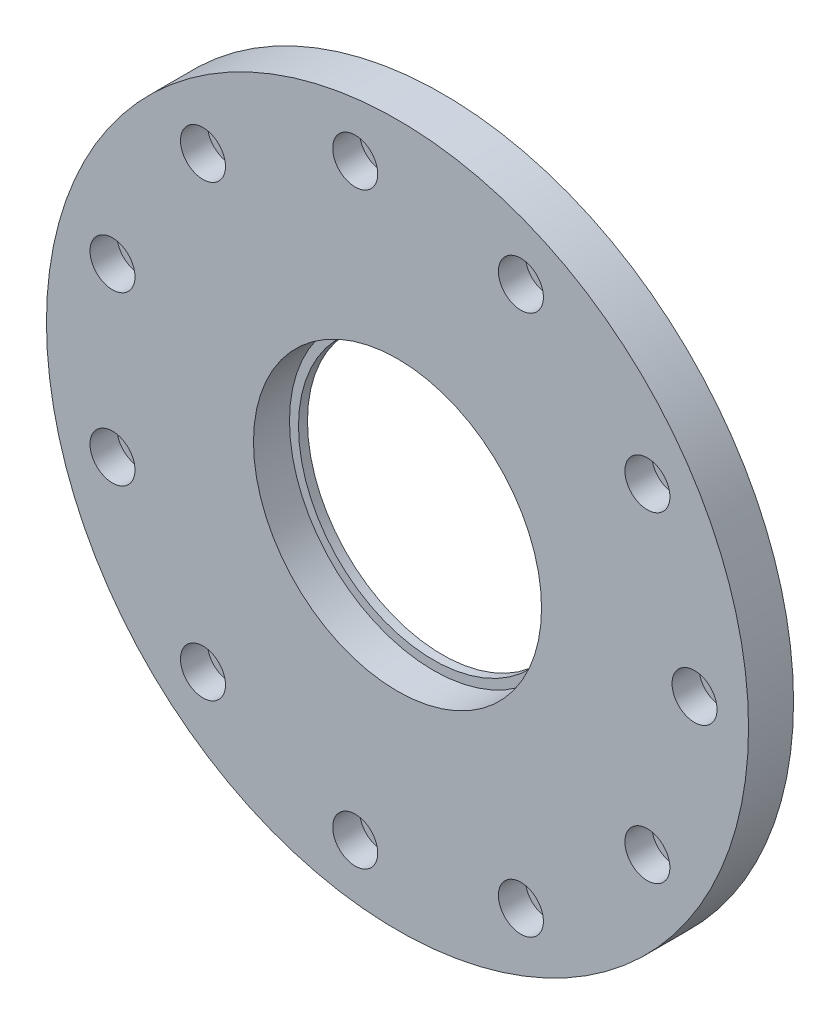
SolidWorks part; units mm, degrees
ref_plane "Front Plane" through (0, 0, 0) normal (0, 0, 1) x (1, 0, 0)
ref_plane "Top Plane" through (0, 0, 0) normal (0, 1, 0) x (1, 0, 0)
ref_plane "Right Plane" through (0, 0, 0) normal (1, 0, 0) x (0, 0, -1)
sketch "Sketch1" plane through (0, 0, 0) normal (0, 0, 1) x (1, 0, 0)
  circle A0 centre (0, 0) radius 39
  circle A1 centre (0, 0) radius 33 construction
  circle A2 centre (33, 0) radius 2.5
  circle A3 centre (27.7614, -17.8411) radius 2.5
  circle A4 centre (13.7087, -30.0179) radius 2.5
  circle A5 centre (-4.6964, -32.6641) radius 2.5
  circle A6 centre (-21.6104, -24.9397) radius 2.5
  circle A7 centre (-31.6633, -9.2972) radius 2.5
  circle A8 centre (-31.6633, 9.2972) radius 2.5
  circle A9 centre (-21.6104, 24.9397) radius 2.5
  circle A10 centre (-4.6964, 32.6641) radius 2.5
  circle A11 centre (13.7087, 30.0179) radius 2.5
  circle A12 centre (27.7614, 17.8411) radius 2.5
  circle A13 centre (0, 0) radius 16
  point P7 (0, 0)
  point P8 (0.7168, 0)
  point P28 (0, 0)
  point P30 (0, 0)
extrude "Boss-Extrude1" add sketch "Sketch1" along normal blind 3
sketch "Sketch2" plane through (0, 0, 0) normal (0, 0, -1) x (-1, 0, 0)
  circle A0 centre (0, 0) radius 16
  circle A1 centre (0, 0) radius 39
  dimension "D1" = 32
extrude "Boss-Extrude2" add sketch "Sketch2" along normal blind 2 contours A1 | A0
sketch "Sketch3" plane through (0, 0, 3) normal (0, 0, 1) x (1, 0, 0)
  circle A0 centre (33, 0) radius 1.6
  circle A1 centre (27.7614, -17.8411) radius 1.6
  circle A2 centre (13.7087, -30.0179) radius 1.6
  circle A3 centre (-4.6964, -32.6641) radius 1.6
  circle A4 centre (-21.6104, -24.9397) radius 1.6
  circle A5 centre (-31.6633, -9.2972) radius 1.6
  circle A6 centre (-31.6633, 9.2972) radius 1.6
  circle A7 centre (-21.6104, 24.9397) radius 1.6
  circle A8 centre (-4.6964, 32.6641) radius 1.6
  circle A9 centre (13.7087, 30.0179) radius 1.6
  circle A10 centre (27.7614, 17.8411) radius 1.6
  point P25 (0, 0)
  dimension "D1" = 3.2
  dimension "D2" = 11
extrude "Cut-Extrude1" cut sketch "Sketch3" against normal through all
sketch "Sketch4" plane through (0, 0, -2) normal (0, 0, -1) x (-1, 0, 0)
  circle A0 centre (0, 0) radius 16
  circle A1 centre (0, 0) radius 15
  dimension "D1" = 32
  dimension "D2" = 30
extrude "Boss-Extrude3" add sketch "Sketch4" against normal blind 1
